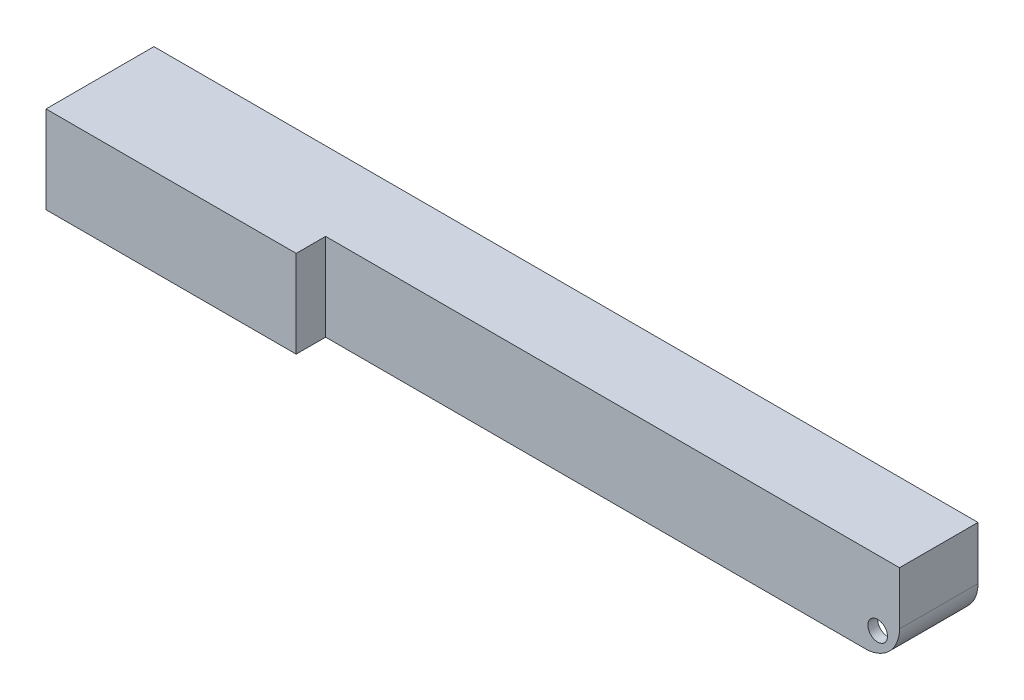
SolidWorks part; units mm, degrees
ref_plane "Front Plane" through (0, 0, 0) normal (0, 0, 1) x (1, 0, 0)
ref_plane "Top Plane" through (0, 0, 0) normal (0, 1, 0) x (1, 0, 0)
ref_plane "Right Plane" through (0, 0, 0) normal (1, 0, 0) x (0, 0, -1)
sketch "Sketch1" plane through (0, 0, 0) normal (0, 1, 0) x (1, 0, 0)
  line L1 (-84, -11) -> (84, -11)
  line L2 (-84, -11) -> (-84, 11)
  line L3 (-84, 11) -> (84, 11)
  line L4 (84, -11) -> (84, 11)
  line L5 (-84, -11) -> (84, 11) construction
  line L6 (-84, 11) -> (84, -11) construction
  point P0 (0, 0)
  dimension "D1" = 22
  dimension "D2" = 168
extrude "Boss-Extrude1" add sketch "Sketch1" against normal blind 17.8 contours L2 L3 L4 L1
sketch "Sketch8" plane through (0, 0, 11) normal (0, 0, 1) x (1, 0, 0)
  line L0 (84, 0) -> (66.2, -17.8) construction
  line L1 (-84, -17.8) -> (84, -17.8) construction
  line L2 (66.2, -17.8) -> (84, -17.8) construction
  line L3 (75.1, -8.9) -> (84, -8.9) construction
  line L4 (84, -17.8) -> (84, 0) construction
  line L5 (79.55, -8.9) -> (79.55, -17.8) construction
  circle A0 centre (79.55, -13.35) radius 2
  dimension "D1" = 4
extrude "Cut-Extrude4" cut sketch "Sketch8" against normal up to surface (22 mm away) up to face at (0, -8.9, -11)
sketch "Sketch5" plane through (0, 0, 0) normal (0, 1, 0) x (1, 0, 0)
  line L0 (-84, -11) -> (84, -11) construction
  line L1 (-33, -5) -> (84, -5)
  line L2 (-33, -5) -> (-33, -11)
  line L3 (-33, -11) -> (84, -11)
  line L4 (84, -5) -> (84, -11)
  line L5 (-33, -5) -> (84, -11) construction
  line L6 (-33, -11) -> (84, -5) construction
  line L7 (84, -11) -> (84, 11) construction
  point P0 (25.5, -8)
  dimension "D1" = 117
  dimension "D2" = 6
extrude "Cut-Extrude2" cut sketch "Sketch5" against normal up to surface (17.8 mm away) up to face at (0, -17.8, 0)
sketch "Sketch6" plane through (0, -17.8, 0) normal (0, -1, 0) x (1, 0, 0)
  line L0 (-82, 9) -> (-82, -9)
  line L1 (-82, -9) -> (82, -9)
  line L5 (-35, 9) -> (-82, 9)
  line L6 (-84, 11) -> (-33, 11) construction
  line L7 (-84, 11) -> (-84, -11) construction
  line L8 (-84, -11) -> (84, -11) construction
  line L13 (82, -9) -> (82, 3)
  line L14 (82, 3) -> (-35, 3)
  line L15 (-35, 3) -> (-35, 9)
  line L16 (84, 5) -> (84, -11) construction
  line L17 (-33, 5) -> (84, 5) construction
  line L18 (-33, 11) -> (-33, 5) construction
  dimension "D1" = 2
  dimension "D2" = 2
  dimension "D3" = 2
  dimension "D4" = 2
  dimension "D5" = 2
  dimension "D6" = 2
extrude "Cut-Extrude3" cut sketch "Sketch6" against normal offset from surface (15.8 mm away) 2 up to face at (-11, 0, 1.6667)
sketch "Sketch9" plane through (0, 0, 9) normal (0, 0, -1) x (-1, 0, 0)
  line L0 (82, -2) -> (82, -17.8) construction
  line L1 (35, -12.3) -> (82, -12.3)
  line L2 (35, -12.3) -> (35, -14.3)
  line L3 (35, -14.3) -> (82, -14.3)
  line L4 (82, -12.3) -> (82, -14.3)
  line L5 (35, -12.3) -> (82, -14.3) construction
  line L6 (35, -14.3) -> (82, -12.3) construction
  line L7 (35, -2) -> (35, -17.8) construction
  line L10 (35, -17.8) -> (82, -17.8) construction
  point P0 (58.5, -13.3)
  dimension "D1" = 2
  dimension "D2" = 3.5
extrude "Boss-Extrude2" add sketch "Sketch9" along normal up to surface (18 mm away) up to face at (0, -9.9, -9)
fillet "Fillet1" radius 7 1 edges at (84, -17.8, -3)
